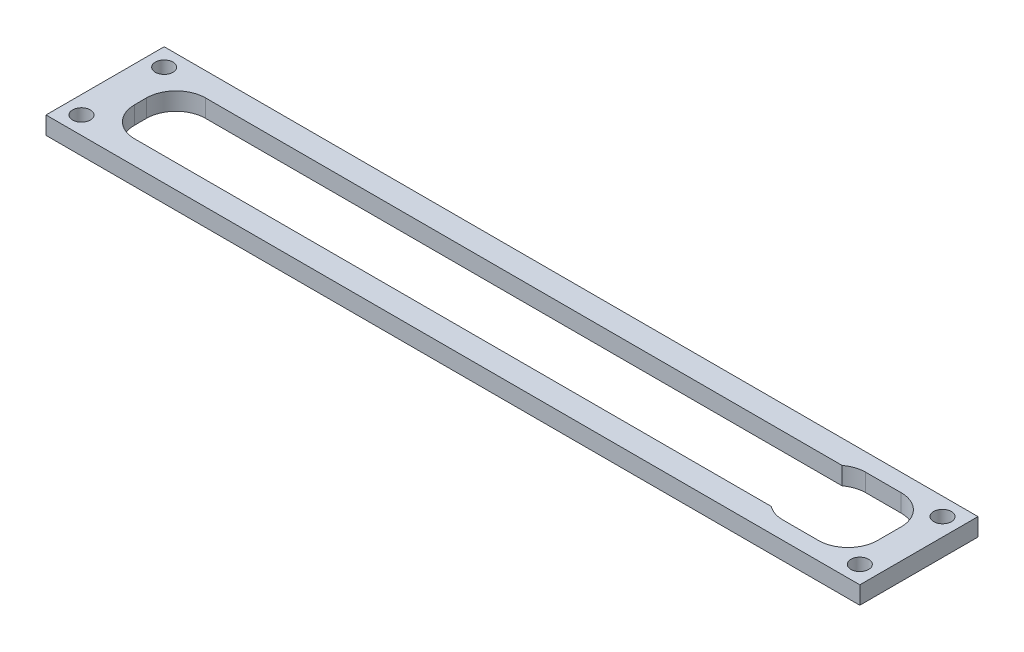
SolidWorks part; units mm, degrees
ref_plane "Front Plane" through (0, 0, 0) normal (0, 0, 1) x (1, 0, 0)
ref_plane "Top Plane" through (0, 0, 0) normal (0, 1, 0) x (1, 0, 0)
ref_plane "Right Plane" through (0, 0, 0) normal (1, 0, 0) x (0, 0, -1)
sketch "Sketch1" plane through (0, 0, 0) normal (0, 1, 0) x (1, 0, 0)
  line L0 (68.8639, 20) -> (68.8639, 0) construction
  line L1 (0, 0) -> (137.7278, 0)
  line L2 (0, 0) -> (0, 20)
  line L3 (0, 20) -> (137.7278, 20)
  line L4 (137.7278, 0) -> (137.7278, 20)
  line L5 (0, 10) -> (137.7278, 10) construction
  line L6 (68.8639, 16) -> (68.8639, 4) construction
  line L7 (6, 16) -> (131.7278, 16)
  line L8 (6, 16) -> (6, 4)
  line L9 (6, 4) -> (131.7278, 4)
  line L10 (131.7278, 16) -> (131.7278, 4)
  line L11 (6, 10) -> (131.7278, 10) construction
  circle A0 centre (3, 17) radius 1.5
  circle A1 centre (3, 3) radius 1.5
  circle A2 centre (134.7278, 3) radius 1.5
  circle A3 centre (134.7278, 17) radius 1.5
  point P17 (68.8639, 10)
  point P18 (68.8639, 10)
  dimension "D7" = 3
  dimension "D1" = 137.7278
  dimension "D2" = 20
  dimension "D3" = 125.7278
  dimension "D4" = 12
  dimension "D5" = 3
  dimension "D6" = 3
extrude "Boss-Extrude1" add sketch "Sketch1" along normal blind 3
sketch "Sketch2" plane through (0, 3, 0) normal (0, 1, 0) x (1, 0, 0)
  line L0 (92, 10) -> (-49908, 10) construction
  line L1 (131.7278, 4) -> (131.7278, 16) construction
  line L2 (118.7278, 17) -> (118.7278, 16)
  line L5 (131.7278, 16) -> (6, 16) construction
  line L6 (125.7278, 17) -> (125.7278, 3) construction
  line L7 (118.7278, 17) -> (132.7278, 17)
  line L9 (118.7278, 3) -> (132.7278, 3)
  line L10 (132.7278, 17) -> (132.7278, 3)
  line L12 (118.7278, 16) -> (131.7278, 16)
  line L13 (131.7278, 16) -> (131.7278, 4)
  line L14 (131.7278, 4) -> (118.7278, 4)
  line L15 (6, 4) -> (131.7278, 4) construction
  line L16 (118.7278, 4) -> (118.7278, 3)
  point P4 (131.7278, 10)
  point P23 (125.7278, 10)
  dimension "D1" = 1
  dimension "D2" = 14
  dimension "D3" = 14
extrude "Cut-Extrude1" cut sketch "Sketch2" against normal through all
fillet "Fillet1" radius 5 6 edges at (132.7278, 1.5, -17) (132.7278, 1.5, -3) (118.7278, 1.5, -17) (118.7278, 1.5, -3) (6, 1.5, -4) (6, 1.5, -16)
equation "\"TrackLength\"= ( ( \"n\" * 28 ) ) / cos ( \"MountAngle\" ) - ( 2 * \"x\" )"
equation "\"D1@Sketch1\"=\"TrackLength\""
equation "\"TrackWidth\"= \"MarbleTrackWidth\" + ( 2 * 4 )"
equation "\"D2@Sketch1\"=\"TrackWidth\""
equation "\"MarbleTrackWidth\"= \"MarbleWidth\" - 1"
equation "\"MarbleTrackLength\"= \"TrackLength\" - ( 2 * 6 )"
equation "\"D3@Sketch1\"=\"MarbleTrackLength\""
equation "\"D4@Sketch1\"=\"MarbleTrackWidth\""
equation "\"MarbleWidth\"= 13"
equation "\"n\"= 5"
equation "\"MountAngle\"= 10"
equation "\"x\"= 14 / cos ( \"MountAngle\" ) - 12"
